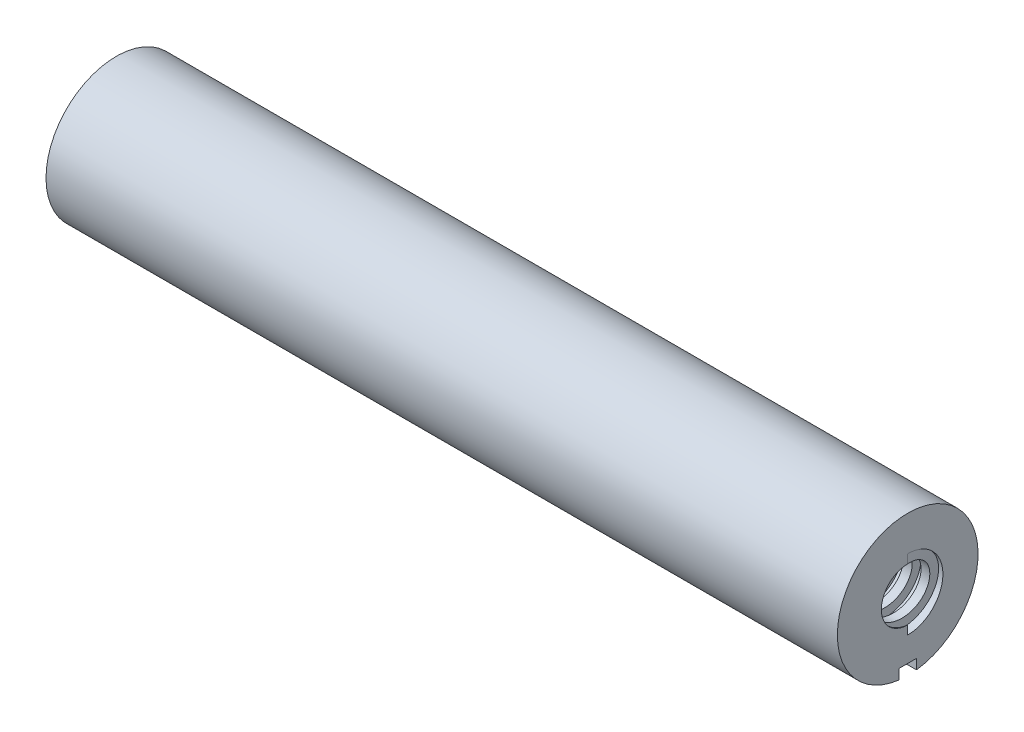
SolidWorks part; units mm, degrees
ref_plane "Front Plane" through (0, 0, 0) normal (0, 0, 1) x (1, 0, 0)
ref_plane "Top Plane" through (0, 0, 0) normal (0, 1, 0) x (1, 0, 0)
ref_plane "Right Plane" through (0, 0, 0) normal (1, 0, 0) x (0, 0, -1)
sketch "Sketch1" plane through (0, 0, 0) normal (0, 0, 1) x (1, 0, 0)
  line L0 (0, 0) -> (225, 0) construction
  line L1 (0, 10) -> (0, 20)
  line L2 (0, 20) -> (225, 20)
  line L3 (225, 20) -> (225, 7.5)
  line L4 (225, 7.5) -> (180, 7.5)
  line L5 (180, 7.5) -> (180, 11)
  line L6 (180, 11) -> (40, 11)
  line L7 (40, 11) -> (40, 9)
  line L8 (40, 9) -> (0, 10)
  point P3 (29.1577, 16.9377)
  dimension "D1" = 225
  dimension "D2" = 40
  dimension "D3" = 20
  dimension "D4" = 40
  dimension "D5" = 18
  dimension "D6" = 22
  dimension "D7" = 45
  dimension "D8" = 15
revolve "Revolve1" add sketch "Sketch1" angle 360 about L0
ref_plane "Plane1" through (235, 0, 0) normal (1, 0, 0) x (0, 0, -1)
sketch "Sketch2" plane through (235, 0, 0) normal (1, 0, 0) x (0, 0, -1)
  circle A0 centre (0, 0) radius 7.5
  circle A1 centre (0, 0) radius 7.5 construction
curve "Helix/Spiral1" pitch 5 height 58.75 radius 7.5 centre (235, 0, 0) axis (-1, 0, 0) start towards (0, 0, -1)
ref_plane "Plane2" through (235, 0, -7.5) normal (-0.1055, -0.9944, 0) x (-0.9944, 0.1055, 0)
sketch "Sketch3" plane through (235, 0, -7.5) normal (-0.1055, -0.9944, 0) x (-0.9944, 0.1055, 0)
  line L1 (-1.25, -2.5) -> (1.25, -2.5)
  line L2 (-1.25, -2.5) -> (-1.25, 2.5)
  line L3 (-1.25, 2.5) -> (1.25, 2.5)
  line L4 (1.25, -2.5) -> (1.25, 2.5)
  line L5 (-1.25, -2.5) -> (1.25, 2.5) construction
  line L6 (-1.25, 2.5) -> (1.25, -2.5) construction
  point P0 (0, 0)
  dimension "D1" = 2.5
  dimension "D2" = 5
sweep "Cut-Sweep1" cut profiles "Sketch3" path "Helix/Spiral1" align with end faces yes
sketch "Sketch4" plane through (225, 0, 0) normal (1, 0, 0) x (0, 0, -1)
  line L1 (-2.5, -23) -> (2.5, -23)
  line L2 (-2.5, -23) -> (-2.5, -17)
  line L3 (-2.5, -17) -> (2.5, -17)
  line L4 (2.5, -23) -> (2.5, -17)
  line L5 (-2.5, -23) -> (2.5, -17) construction
  line L6 (-2.5, -17) -> (2.5, -23) construction
  circle A0 centre (0, 0) radius 20 construction
  point P0 (0, -20)
  dimension "D1" = 5
  dimension "D2" = 6
extrude "Cut-Extrude1" cut sketch "Sketch4" against normal blind 205
